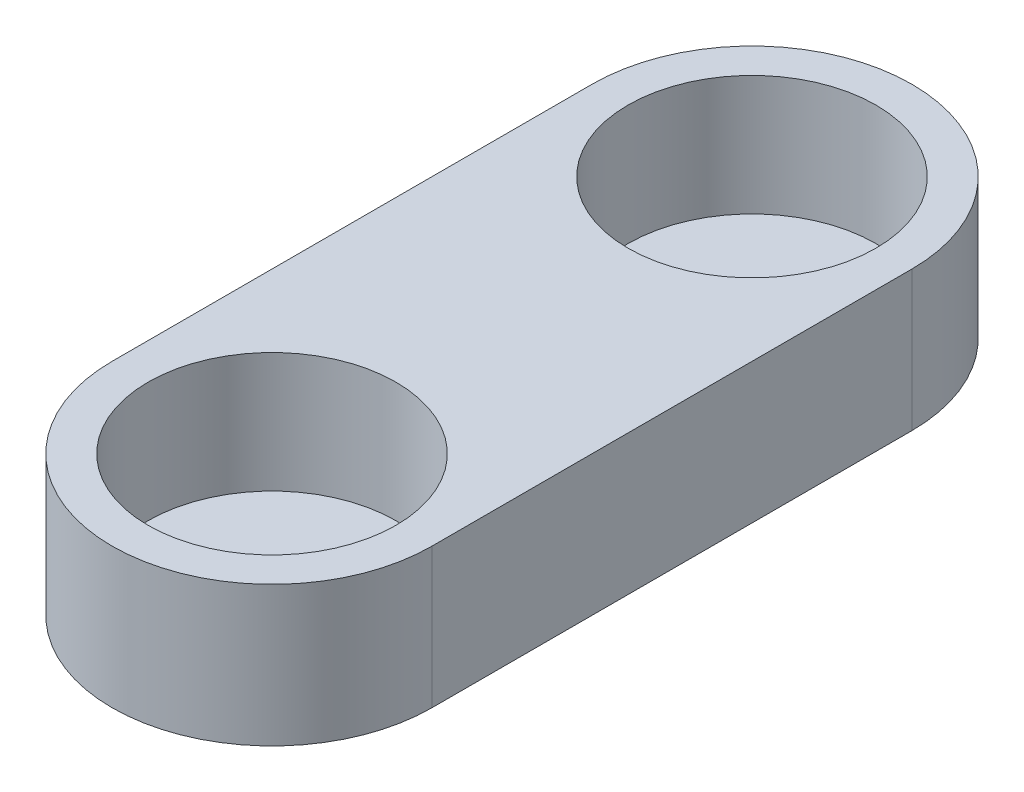
SolidWorks part; units mm, degrees
ref_plane "Front Plane" through (0, 0, 0) normal (0, 0, 1) x (1, 0, 0)
ref_plane "Top Plane" through (0, 0, 0) normal (0, 1, 0) x (1, 0, 0)
ref_plane "Right Plane" through (0, 0, 0) normal (1, 0, 0) x (0, 0, -1)
sketch "Sketch1" plane through (0, 0, 0) normal (0, 1, 0) x (1, 0, 0)
  line L0 (0, 6) -> (0, -6) construction
  line L1 (4, 6) -> (4, -6)
  line L2 (-4, 6) -> (-4, -6)
  arc A1 (4, 6) -> (-4, 6) centre (0, 6) ccw
  arc A2 (-4, -6) -> (4, -6) centre (0, -6) ccw
  circle A3 centre (0, 6) radius 3.1
  circle A4 centre (0, -6) radius 3.1
  point P5 (0, 0)
  dimension "D2" = 6.2
  dimension "D3" = 4
  dimension "D4" = 12
extrude "Boss-Extrude1" add sketch "Sketch1" along normal blind 3
sketch "Sketch2" plane through (0, 0, 0) normal (0, -1, 0) x (1, 0, 0)
  line L0 (0, 6) -> (0, -6) construction
  line L1 (4, 6) -> (4, -6)
  line L2 (-4, 6) -> (-4, -6)
  arc A0 (4, 6) -> (-4, 6) centre (0, 6) ccw
  arc A1 (-4, -6) -> (4, -6) centre (0, -6) ccw
  point P4 (0, 0)
extrude "Boss-Extrude2" add sketch "Sketch2" along normal blind 0.5
sketch "Sketch3" plane through (0, -0.5, 0) normal (0, -1, 0) x (1, 0, 0)
  circle A0 centre (0, 0) radius 0.8
  dimension "D1" = 1.6
extrude "Cut-Extrude1" cut sketch "Sketch3" against normal blind 2.5
